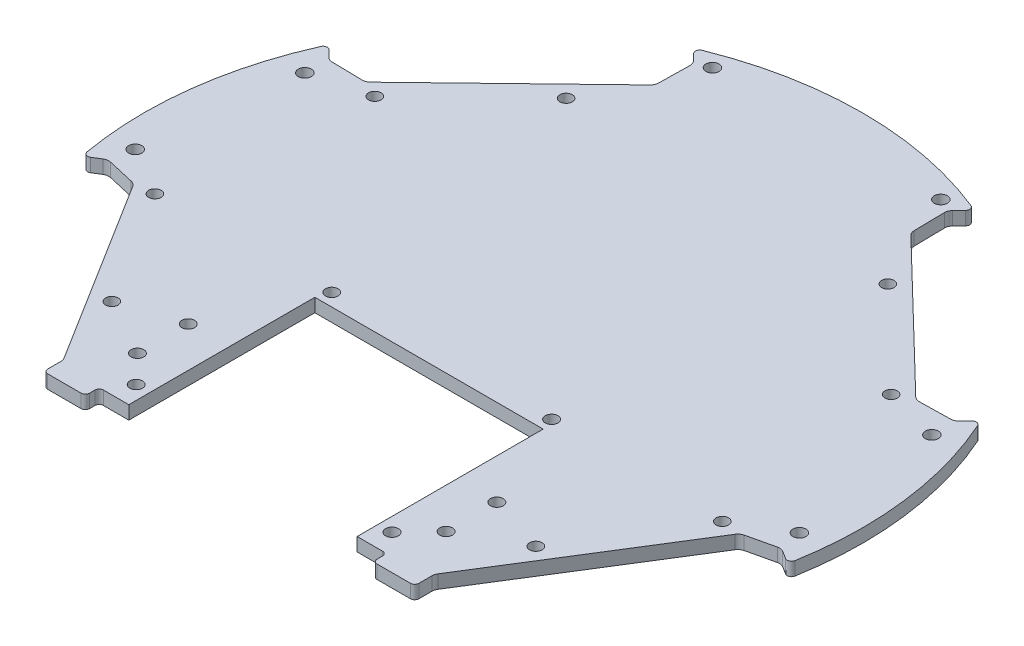
SolidWorks part; units mm, degrees
note: '?' marks a value the reader was unsure of.
material "6061 Alloy"
ref_plane "Front Plane" through (0, 0, 0) normal (0, 0, 1) x (1, 0, 0)
ref_plane "Top Plane" through (0, 0, 0) normal (0, 1, 0) x (1, 0, 0)
ref_plane "Right Plane" through (0, 0, 0) normal (1, 0, 0) x (0, 0, -1)
sketch "Sketch1" plane through (0, 0, 0) normal (0, 1, 0) x (1, 0, 0)
  line L0 (0, 0) -> (0, -62.55) construction
  line L1 (-83.4462, -16.178) -> (-71.2857, -8.5793) construction
  line L6 (0, 0) -> (-59.046, 61.1439) construction
  line L7 (0, 0) -> (-72.0841, -45.0431) construction
  line L8 (-33.174, 78.2591) -> (-23.2129, 67.9442) construction
  line L9 (-72.0841, -45.0431) -> (-70.388, -43.9833) construction
  line L10 (-70.388, -43.9833) -> (-84.9608, -20.662) construction
  line L11 (-84.9608, -20.662) -> (-72.2401, -12.7132) construction
  line L12 (-72.2401, -12.7132) -> (-43.0945, -59.3558) construction
  line L13 (-43.0945, -59.3558) -> (-55.8152, -67.3046) construction
  line L14 (-55.8152, -67.3046) -> (-70.388, -43.9833) construction
  line L21 (-59.046, 61.1439) -> (-57.6566, 59.7052)
  line L22 (-77.4385, 40.6021) -> (-37.8748, 78.8083) construction
  line L23 (-73.9694, 32.6911) -> (-77.0537, 35.885)
  line L24 (-37.8748, 78.8083) -> (-27.4549, 68.0182) construction
  line L25 (-27.4549, 68.0182) -> (-67.0186, 29.812) construction
  line L26 (-67.0186, 29.812) -> (-77.4385, 40.6021) construction
  line L27 (-43.0945, -64.8266) -> (-34, -64.8266)
  line L33 (-86.5505, -18.1178) -> (-71.2857, -8.5793) construction
  line L34 (0, 0) -> (0, 50000) construction
  line L35 (0, 0) -> (-50000, 0) construction
  line L36 (-57.5543, -62.55) -> (-19.8595, -62.55) construction
  line L38 (-67.0927, 25.57) -> (-79.5965, 38.5181) construction
  line L39 (-54.9774, -64.8266) -> (0, -64.8266) construction
  line L40 (-35.7168, 80.8923) -> (-23.2129, 67.9442) construction
  line L41 (-38.9606, -60.3102) -> (-54.2255, -69.8488) construction
  line L42 (-34, -62.55) -> (-19.8595, -62.55) construction
  line L43 (-43.0945, -64.8266) -> (-43.0945, -58.4123) construction
  line L45 (73.9694, 32.6911) -> (77.0537, 35.885)
  line L46 (-71.2857, -8.5793) -> (-38.9606, -60.3102) construction
  line L47 (83.4462, -16.178) -> (79.6809, -13.8252)
  line L48 (69.4846, -16.1792) -> (43.8945, -57.132)
  line L50 (43.0945, -64.8266) -> (34, -64.8266)
  line L51 (34, -62.55) -> (34, -64.8266)
  line L52 (0, 0) -> (72.0841, -45.0431) construction
  line L53 (0, 0) -> (59.046, 61.1439) construction
  line L54 (-30.0897, 75.0653) -> (-30.2847, 63.8954)
  line L55 (-62.7996, 32.4961) -> (-30.2847, 63.8954)
  line L56 (-30.0897, 75.0653) -> (-33.174, 78.2591)
  line L57 (73.9694, 32.6911) -> (77.0537, 35.885)
  line L58 (30.0897, 75.0653) -> (33.174, 78.2591)
  line L59 (-34, -62.55) -> (-34, -61.55)
  line L60 (62.7996, 32.4961) -> (30.2847, 63.8954)
  line L61 (-73.9694, 32.6911) -> (-62.7996, 32.4961)
  line L62 (-77.0537, 35.885) -> (-67.0927, 25.57) construction
  line L63 (-83.4462, -16.178) -> (-79.6809, -13.8252)
  line L64 (-79.6809, -13.8252) -> (-69.4846, -16.1792)
  line L65 (-69.4846, -16.1792) -> (-43.8945, -57.132)
  line L66 (-27.4549, 68.0182) -> (-23.2129, 67.9442) construction
  line L67 (-72.2401, -12.7132) -> (-71.2857, -8.5793) construction
  line L68 (30.0897, 75.0653) -> (30.2847, 63.8954)
  line L69 (73.9694, 32.6911) -> (62.7996, 32.4961)
  line L70 (-34, -62.55) -> (-34, -64.8266)
  line L71 (79.6809, -13.8252) -> (69.4846, -16.1792)
  line L72 (-34, -61.55) -> (-20, -61.55)
  line L73 (-20, -61.55) -> (-19.8595, -62.55)
  line L74 (-19.8595, -62.55) -> (19.8595, -62.55)
  line L75 (20, -61.55) -> (19.8595, -62.55)
  line L76 (34, -61.55) -> (20, -61.55)
  line L77 (34, -62.55) -> (34, -61.55)
  line L78 (-43.0945, -64.8266) -> (-43.8945, -64.8266)
  line L79 (-19.8595, -62.55) -> (0, -62.55) construction
  line L80 (-19.8595, -62.55) -> (34, -62.55) construction
  line L81 (-43.8945, -64.8266) -> (-43.8945, -57.132)
  line L82 (-43.0945, -58.4123) -> (-43.8945, -57.132) construction
  line L83 (43.8945, -64.8266) -> (43.8945, -57.132)
  line L84 (43.0945, -64.8266) -> (43.8945, -64.8266)
  line L97 (-23.2129, 67.9442) -> (-67.0927, 25.57) construction
  circle A0 centre (0, 0) radius 85 construction
  circle A1 centre (0, 0) radius 90 construction
  arc A51 (-77.0537, 35.885) -> (-83.4462, -16.178) centre (0, 0) ccw
  arc A52 (77.0537, 35.885) -> (83.4462, -16.178) centre (0, 0) cw
  arc A54 (-33.174, 78.2591) -> (33.174, 78.2591) centre (0, 0) cw
  point P29 (-31.6318, 76.6622)
  point P33 (-47.2368, 48.9151)
  point P34 (31.6318, 76.6622)
  point P35 (-57.6673, -36.0345)
  point P85 (-57.6566, 59.7052)
  dimension "D2" = 58
  dimension "D10" = 82
  dimension "D12" = 170
  dimension "D14" = 34
  dimension "D13" = 1
  dimension "D15" = 3
  dimension "D3" = 180
  dimension "D4" = 64.8266
  dimension "D5" = 44
  dimension "D6" = 15
  dimension "D7" = 55
  dimension "D8" = 62.55
  dimension "D9" = 2
  dimension "D11" = 2
  dimension "D16" = 7
  dimension "D17" = 7
  dimension "D18" = 0.5
  dimension "D19" = 1
  dimension "D20" = 14
  dimension "D21" = 0.8
extrude "Boss-Extrude4" add sketch "Sketch1" along normal mid plane 3.175
ref_point "Rear_Axle_Center (L)"
ref_axis "Rear_Axle_Proj (L)" through (46.5421, 0, -48.1958) along (0, 1, 0)?
ref_point "Front_Axle_Center (L)"
ref_axis "Front_Axle_Proj (L)" through (57.2432, 0, 35.7696) along (0, 1, 0)?
ref_point "Front_Axle_Center (R)"
ref_axis "Front_Axle_Proj (R)" through (-57.2432, 0, 35.7696) along (0, 1, 0)?
ref_point "Read_Axle_Center (R)"
ref_axis "Rear_Axle_Proj (R)" through (-46.5421, 0, -48.1958) along (0, 1, 0)?
sketch "Sketch17" plane through (0, 1.5875, 0) normal (0, 1, 0) x (1, 0, 0)
  line L0 (0, -57.55) -> (0, -62.55) construction
  line L1 (-19.8595, -62.55) -> (19.8595, -62.55) construction
  circle A0 centre (0, -57.55) radius 8.5
  dimension "D1" = 17
  dimension "D2" = 5
extrude "Boss-Extrude5" [suppressed] add sketch "Sketch17" against normal up to surface (3.175 mm away)
ref_plane "Plane1" through (0, 0, 10) normal (0, 0, 1) x (1, 0, 0)
hole_wizard "M3 Clearance Hole3" positions "Sketch18" profile "Sketch19" hole size "M3" standard "ANSI Metric" end condition through all
sketch "Sketch18" plane through (0, -1.5875, 0) normal (0, -1, 0) x (-1, 0, 0)
  line L0 (-36.5, -50) -> (-36.5, -38) construction
  line L3 (0, 0) -> (0, -38) construction
  line L4 (36.5, -50) -> (36.5, -38) construction
  line L6 (0, -38) -> (36.5, -38) construction
  line L8 (0, -38) -> (-36.5, -38) construction
  line L9 (-36.5, -44) -> (36.5, -44) construction
  line L10 (0, -44) -> (0, 0) construction
  point P1 (36.5, -50)
  point P3 (36.5, -38)
  point P5 (-36.5, -50)
  point P33 (-36.5, -38)
  dimension "D1" = 12
  dimension "D2" = 73
  dimension "D4" = 38
sketch "Sketch19" plane through (-36.5, -1.5875, 50) normal (1, 0, 0) x (0, 0, -1)
  line L0 (0, 0) -> (0, 3.175)
  line L1 (0, 3.175) -> (1.5, 3.175)
  line L2 (1.5, 3.175) -> (1.5, 0)
  line L5 (1.5, 0) -> (0, 0)
  line L11 (0, -6.35) -> (0, 107.95) construction
  dimension "Thru Hole Dia." = 3
  dimension "Thru Hole Depth" = 3.175
hole_wizard "M3 Clearance Hole1" positions "Sketch11" profile "Sketch12" hole size "M3" standard "ANSI Metric" end condition through all
sketch "Sketch11" plane through (0, 1.5875, 0) normal (0, 1, 0) x (1, 0, 0)
  line L0 (83.4462, -16.178) -> (79.6809, -13.8252) construction
  line L2 (73.9694, 32.6911) -> (77.0537, 35.885) construction
  line L4 (-73.9694, 32.6911) -> (-77.0537, 35.885) construction
  line L6 (0, 0) -> (0, -50000) construction
  line L7 (78.4111, 9.6277) -> (84.3664, 10.3589) construction
  line L10 (74.155, 27.2403) -> (78.5423, -8.4914) construction
  line L12 (78.4111, 9.6277) -> (76.3487, 9.3744) construction
  arc A7 (77.964, -12.7523) -> (72.563, 31.2347) centre (0, 0) ccw construction
  arc A13 (-77.964, -12.7523) -> (-72.563, 31.2347) centre (0, 0) cw construction
  arc A17 (83.4462, -16.178) -> (77.0537, 35.885) centre (0, 0) ccw construction
  point P34 (78.5423, -8.4914)
  point P66 (74.155, 27.2403)
  point P70 (-74.155, 27.2403)
  point P71 (-78.5423, -8.4914)
  dimension "D1" = 6
  dimension "D2" = 36
sketch "Sketch12" plane through (-78.5423, 1.5875, 8.4914) normal (1, 0, 0) x (0, 0, 1)
  line L0 (0, 0) -> (0, 3.175)
  line L1 (0, 3.175) -> (1.55, 3.175)
  line L2 (1.55, 3.175) -> (1.55, 0)
  line L5 (1.55, 0) -> (0, 0)
  line L11 (0, -6.35) -> (0, 107.95) construction
  dimension "Thru Hole Dia." = 3.1
  dimension "Thru Hole Depth" = 3.175
hole_wizard "M3 Clearance Hole4" positions "Sketch9" profile "Sketch10" hole size "M3" standard "ANSI Metric" end condition through all
sketch "Sketch9" plane through (0, -1.5875, 0) normal (0, -1, 0) x (-1, 0, 0)
  line L0 (0, 0) -> (0, 63.4318) construction
  line L1 (-38.0437, 52.9272) -> (38.0437, 52.9272) construction
  line L3 (61.0625, 30.6981) -> (-61.0625, 30.6981) construction
  line L4 (-67.0993, -15.2789) -> (67.0993, -15.2789) construction
  line L5 (50.1419, -42.4164) -> (-50.1419, -42.4164) construction
  line L6 (-61.0625, 30.6981) -> (-38.0437, 52.9272) construction
  line L7 (38.0437, 52.9272) -> (61.0625, 30.6981) construction
  line L8 (67.0993, -15.2789) -> (50.1419, -42.4164) construction
  line L9 (-50.1419, -42.4164) -> (-67.0993, -15.2789) construction
  line L10 (0, 0) -> (-44.8055, 46.3974) construction
  line L11 (0, 0) -> (44.8055, 46.3974) construction
  line L12 (0, 0) -> (-96.9468, 0) construction
  line L14 (-55.1231, -34.4448) -> (0, 0) construction
  line L15 (0, 0) -> (55.1231, -34.4448) construction
  line L18 (-69.4846, -16.1792) -> (-43.8945, -57.132) construction
  line L19 (-62.7996, 32.4961) -> (-30.2847, 63.8954) construction
  point P0 (-67.0993, -15.2789)
  point P2 (-50.1419, -42.4164)
  point P9 (-61.0625, 30.6981)
  point P11 (-38.0437, 52.9272)
  point P30 (50.1419, -42.4164)
  point P31 (67.0993, -15.2789)
  point P32 (38.0437, 52.9272)
  point P33 (61.0625, 30.6981)
  dimension "D9" = 46
  dimension "D10" = 46
  dimension "D11" = 32
  dimension "D12" = 32
  dimension "D7" = 58
  dimension "D5" = 32
  dimension "D6" = 2.5
  dimension "D8" = 9.4
  dimension "D2" = 44
  dimension "D3" = 32
  dimension "D4" = 2.5
  dimension "D13" = 9.4
sketch "Sketch10" plane through (67.0993, -1.5875, 15.2789) normal (1, 0, 0) x (0, 0, -1)
  line L0 (0, 0) -> (0, 3.175)
  line L1 (0, 3.175) -> (1.475, 3.175)
  line L2 (1.475, 3.175) -> (1.475, 0)
  line L5 (1.475, 0) -> (0, 0)
  line L11 (0, -6.35) -> (0, 107.95) construction
  dimension "Thru Hole Dia." = 2.95
  dimension "Thru Hole Depth" = 3.175
hole_wizard "M3 Clearance Hole2" positions "Sketch13" profile "Sketch14" hole size "M3" standard "ANSI Metric" end condition through all
sketch "Sketch13" plane through (0, 1.5875, 0) normal (0, 1, 0) x (1, 0, 0)
  line L0 (0, 0) -> (0, 85) construction
  line L2 (-24, 47) -> (-24, 81) construction
  line L3 (-24, 47) -> (24, 47) construction
  line L4 (-24, 81) -> (24, 81) construction
  line L5 (24, 47) -> (24, 81) construction
  line L6 (-24, 47) -> (24, 81) construction
  line L7 (-24, 81) -> (24, 47) construction
  line L8 (-38.0437, 52.9272) -> (-61.0625, 30.6981) construction
  line L10 (-36.307, 51.1289) -> (-59.3259, 28.8998) construction
  line L11 (-16.3488, 39.8187) -> (-31.6313, 55.6441) construction
  line L12 (-16.3488, 39.8187) -> (-48.7191, 8.559) construction
  line L13 (-31.6313, 55.6441) -> (-64.0016, 24.3845) construction
  line L14 (-48.7191, 8.559) -> (-64.0016, 24.3845) construction
  line L15 (-16.3488, 39.8187) -> (-64.0016, 24.3845) construction
  line L16 (-31.6313, 55.6441) -> (-48.7191, 8.559) construction
  line L17 (-49.5531, 41.8127) -> (-40.1752, 32.1016) construction
  line L18 (-27, 76.4978) -> (-27, 80.5978) construction
  arc A0 (33.174, 78.2591) -> (-33.174, 78.2591) centre (0, 0) ccw construction
  circle A1 centre (-16.2162, 44) radius 3 construction
  circle A2 centre (-27, 76.4978) radius 3 construction
  point P65 (0, 64)
  point P181 (-27, 76.4978)
  point P184 (27, 76.4978)
  dimension "D7" = 6
  dimension "D1" = 48
  dimension "D2" = 34
  dimension "D3" = 4
  dimension "D5" = 45
  dimension "D6" = 22
  dimension "D8" = 4.1
  dimension "D4" = 2.5
sketch "Sketch14" plane through (27, 1.5875, -76.4978) normal (1, 0, 0) x (0, 0, 1)
  line L0 (0, 0) -> (0, 3.175)
  line L1 (0, 3.175) -> (1.55, 3.175)
  line L2 (1.55, 3.175) -> (1.55, 0)
  line L5 (1.55, 0) -> (0, 0)
  line L11 (0, -6.35) -> (0, 107.95) construction
  dimension "Thru Hole Dia." = 3.1
  dimension "Thru Hole Depth" = 3.175
hole_wizard "M3 Clearance Hole5" [suppressed] positions "Sketch24" profile "Sketch25" hole size "M3" standard "ANSI Metric"
sketch "Sketch24" plane through (0, 1.5875, 0) normal (0, 1, 0) x (1, 0, 0)
  line L1 (-11, -4.4) -> (11, -4.4) construction
  line L2 (11, -4.4) -> (11, -36.4) construction
  line L3 (11, -36.4) -> (-11, -36.4) construction
  line L4 (-11, -36.4) -> (-11, -4.4) construction
  line L7 (-11, 37.6) -> (11, 37.6) construction
  line L8 (0, -4.4) -> (0, 0) construction
  line L9 (0, 0) -> (0, 37.6) construction
  point P8 (-11, -4.4)
  point P10 (11, -4.4)
  point P12 (11, -36.4)
  point P14 (-11, -36.4)
  point P42 (-11, 37.6)
  point P45 (11, 37.6)
  dimension "D1" = 22
  dimension "D2" = 32
  dimension "D3" = 4.4
  dimension "D4" = 42
sketch "Sketch25" plane through (-11, 1.5875, 4.4) normal (1, 0, 0) x (0, 0, 1)
  line L0 (0, 0) -> (0, 3.175)
  line L1 (0, 3.175) -> (1.5, 3.175)
  line L2 (1.5, 3.175) -> (1.5, 0)
  line L5 (1.5, 0) -> (0, 0)
  line L11 (0, -6.35) -> (0, 107.95) construction
  dimension "Thru Hole Dia." = 3
  dimension "Thru Hole Depth" = 3.175
sketch "Sketch20" plane through (0, 1.5875, 0) normal (0, 1, 0) x (1, 0, 0)
  line L0 (-16.1485, 44) -> (-16.1485, 39) construction
  line L1 (-14.6485, 44) -> (-14.6485, 39)
  line L2 (-17.6485, 44) -> (-17.6485, 39)
  line L3 (0, 0) -> (0, 85) construction
  line L5 (16.1485, 44) -> (16.1485, 39) construction
  line L6 (14.6485, 44) -> (14.6485, 39)
  line L7 (17.6485, 44) -> (17.6485, 39)
  arc A0 (-14.6485, 44) -> (-17.6485, 44) centre (-16.1485, 44) ccw
  arc A1 (-17.6485, 39) -> (-14.6485, 39) centre (-16.1485, 39) ccw
  arc A5 (33.174, 78.2591) -> (-33.174, 78.2591) centre (0, 0) ccw construction
  arc A7 (14.6485, 44) -> (17.6485, 44) centre (16.1485, 44) cw
  arc A8 (17.6485, 39) -> (14.6485, 39) centre (16.1485, 39) cw
  point P2 (-16.1485, 41.5)
  point P16 (16.1485, 41.5)
  dimension "D1" = 44
  dimension "D2" = 3
  dimension "D3" = 5
  dimension "D4" = 16.1485
extrude "Cut-Extrude1" [suppressed] cut sketch "Sketch20" against normal through all
sketch "Sketch22" plane through (0, 1.5875, 0) normal (0, 1, 0) x (1, 0, 0)
  line L0 (-56.6896, -36.6556) -> (-58.0464, -37.5035) construction
  line L1 (-69.4846, -16.1792) -> (-43.8945, -57.132) construction
  line L3 (30.2452, 66.1578) -> (65.062, 32.5356)
  line L4 (71.6894, -15.6702) -> (43.8945, -60.1514)
  line L5 (-19.8595, -62.55) -> (19.8595, -62.55) construction
  line L6 (-43.8945, -64.8266) -> (-43.8945, -57.132) construction
  line L28 (-30.2452, 66.1578) -> (-65.062, 32.5356)
  line L29 (-71.6894, -15.6702) -> (-43.8945, -60.1514)
  line L30 (-79.6809, -13.8252) -> (-69.4846, -16.1792) construction
  line L31 (0, 85) -> (0, -62.55) construction
  line L32 (-46.5421, 48.1958) -> (-47.6536, 49.3467) construction
  line L37 (-20, -61.55) -> (-19.8595, -62.55)
  line L38 (-20, -61.55) -> (-19.8595, -62.55)
  line L40 (-43.8945, -57.132) -> (-43.8945, -64.8266)
  line L41 (-43.8945, -57.132) -> (-43.8945, -64.8266)
  line L43 (43.8945, -64.8266) -> (43.8945, -57.132)
  line L44 (43.8945, -64.8266) -> (43.8945, -57.132)
  line L56 (-19.8595, -62.55) -> (19.8595, -62.55)
  line L58 (19.8595, -62.55) -> (20, -61.55)
  line L59 (20, -61.55) -> (34, -61.55)
  line L60 (34, -61.55) -> (34, -64.8266)
  line L61 (34, -64.8266) -> (43.8945, -64.8266)
  line L63 (43.8945, -57.132) -> (69.4846, -16.1792)
  line L64 (69.4846, -16.1792) -> (79.6809, -13.8252)
  line L65 (79.6809, -13.8252) -> (83.4462, -16.178)
  line L66 (77.0537, 35.885) -> (73.9694, 32.6911)
  line L67 (73.9694, 32.6911) -> (62.7996, 32.4961)
  line L68 (62.7996, 32.4961) -> (30.2847, 63.8954)
  line L69 (30.2847, 63.8954) -> (30.0897, 75.0653)
  line L70 (30.0897, 75.0653) -> (33.174, 78.2591)
  line L71 (-33.174, 78.2591) -> (-30.0897, 75.0653)
  line L72 (-30.0897, 75.0653) -> (-30.2847, 63.8954)
  line L73 (-30.2847, 63.8954) -> (-62.7996, 32.4961)
  line L74 (-62.7996, 32.4961) -> (-73.9694, 32.6911)
  line L75 (-73.9694, 32.6911) -> (-77.0537, 35.885)
  line L76 (-83.4462, -16.178) -> (-79.6809, -13.8252)
  line L77 (-79.6809, -13.8252) -> (-69.4846, -16.1792)
  line L78 (-69.4846, -16.1792) -> (-43.8945, -57.132)
  line L80 (-43.8945, -64.8266) -> (-34, -64.8266)
  line L81 (-34, -64.8266) -> (-34, -61.55)
  line L82 (-34, -61.55) -> (-20, -61.55)
  line L84 (-19.8595, -62.55) -> (19.8595, -62.55)
  line L86 (19.8595, -62.55) -> (20, -61.55)
  line L87 (20, -61.55) -> (34, -61.55)
  line L88 (34, -61.55) -> (34, -64.8266)
  line L89 (34, -64.8266) -> (43.8945, -64.8266)
  line L91 (43.8945, -57.132) -> (69.4846, -16.1792)
  line L92 (69.4846, -16.1792) -> (79.6809, -13.8252)
  line L93 (79.6809, -13.8252) -> (83.4462, -16.178)
  line L94 (77.0537, 35.885) -> (73.9694, 32.6911)
  line L95 (73.9694, 32.6911) -> (62.7996, 32.4961)
  line L96 (62.7996, 32.4961) -> (30.2847, 63.8954)
  line L97 (30.2847, 63.8954) -> (30.0897, 75.0653)
  line L98 (30.0897, 75.0653) -> (33.174, 78.2591)
  line L99 (-33.174, 78.2591) -> (-30.0897, 75.0653)
  line L100 (-30.0897, 75.0653) -> (-30.2847, 63.8954)
  line L101 (-30.2847, 63.8954) -> (-62.7996, 32.4961)
  line L102 (-62.7996, 32.4961) -> (-73.9694, 32.6911)
  line L103 (-73.9694, 32.6911) -> (-77.0537, 35.885)
  line L104 (-83.4462, -16.178) -> (-79.6809, -13.8252)
  line L105 (-79.6809, -13.8252) -> (-69.4846, -16.1792)
  line L106 (-69.4846, -16.1792) -> (-43.8945, -57.132)
  line L108 (-43.8945, -64.8266) -> (-34, -64.8266)
  line L109 (-34, -64.8266) -> (-34, -61.55)
  line L110 (-34, -61.55) -> (-20, -61.55)
  arc A9 (83.4462, -16.178) -> (77.0537, 35.885) centre (0, 0) ccw
  arc A10 (33.174, 78.2591) -> (-33.174, 78.2591) centre (0, 0) ccw
  arc A11 (-77.0537, 35.885) -> (-83.4462, -16.178) centre (0, 0) ccw
  arc A13 (83.4462, -16.178) -> (77.0537, 35.885) centre (0, 0) ccw
  arc A14 (33.174, 78.2591) -> (-33.174, 78.2591) centre (0, 0) ccw
  arc A15 (-77.0537, 35.885) -> (-83.4462, -16.178) centre (0, 0) ccw
  dimension "D2" = 1.6
  dimension "D1" = 0
extrude "Boss-Extrude6" add sketch "Sketch22" against normal up to surface (3.175 mm away) up to face at (-27, -1.5875, -74.9478)
fillet "Fillet1" radius 2 14 edges at (-30.0897, 0, -75.0653) (30.0897, 0, -75.0653) (-79.6809, 0, 13.8252) (79.6809, 0, 13.8252) (73.9694, 0, -32.6911) (-73.9694, 0, -32.6911) (65.062, 0, -32.5356) (30.2452, 0, -66.1578) (71.6894, 0, 15.6702) (-71.6894, 0, 15.6702) (-65.062, 0, -32.5356) (-30.2452, 0, -66.1578) (43.8945, 0, 60.1514) (-43.8945, 0, 60.1514)
fillet "Fillet3" radius 1 12 edges at (-77.0537, 0, -35.885) (77.0537, 0, -35.885) (83.4462, 0, 16.178) (34, 0, 64.8266) (-34, 0, 64.8266) (-33.174, 0, -78.2591) (33.174, 0, -78.2591) (-83.4462, 0, 16.178) (34, 0, 61.55) (-34, 0, 61.55) (-43.8945, 0, 64.8266) (43.8945, 0, 64.8266)
sketch "Sketch23" [suppressed] plane through (0, 3.175, 0) normal (0, 1, 0) x (1, 0, 0)
  circle A0 centre (0, -53.55) radius 4.95
  dimension "D1" = 9.9
fillet "Fillet6" radius 0.5 4 edges at (20, 0, 61.55) (19.8595, 0, 62.55) (-20, 0, 61.55) (-19.8595, 0, 62.55)
sketch "Sketch28" plane through (0, 1.5875, 0) normal (0, 1, 0) x (1, 0, 0)
  line L0 (-19.4248, -62.55) -> (19.4248, -62.55) construction
  line L1 (-19.4248, -62.55) -> (19.4248, -62.55) construction
  line L2 (-27, -62.55) -> (27, -62.55)
  line L3 (-27, -62.55) -> (-27, -17.55)
  line L4 (27, -62.55) -> (27, -17.55)
  line L5 (-27, -17.55) -> (27, -17.55)
  line L6 (0, 15.921) -> (0, -77.8833) construction
  arc A0 (19.4248, -62.55) -> (19.9199, -62.1196) centre (19.4248, -62.05) ccw construction
  point P11 (0, -62.55)
  point P16 (0, -17.55)
  dimension "D1" = 54
  dimension "D2" = 45
extrude "Cut-Extrude4" cut sketch "Sketch28" against normal blind 10
extrude "Cut-Extrude2" [suppressed] cut sketch "Sketch23" against normal through all
sketch "Sketch26" [suppressed] plane through (0, 3.175, 0) normal (0, 1, 0) x (1, 0, 0)
  line L0 (0, 0) -> (0, 50) construction
  line L1 (-92.5, 5) -> (92.5, 5)
  line L2 (-92.5, 5) -> (-92.5, 95)
  line L3 (-92.5, 95) -> (92.5, 95)
  line L4 (92.5, 5) -> (92.5, 95)
  line L5 (-92.5, 5) -> (92.5, 95) construction
  line L6 (-92.5, 95) -> (92.5, 5) construction
  point P0 (0, 50)
  dimension "D1" = 90
  dimension "D2" = 185
  dimension "D3" = 5
extrude "Cut-Extrude3" [suppressed] cut sketch "Sketch26" against normal through all
fillet "Fillet4" [suppressed] radius 5
sketch "Sketch29" plane through (0, 1.5875, 0) normal (0, 1, 0) x (1, 0, 0)
  line L0 (-27, -61.55) -> (-27, -56.55)
  line L2 (-27, -17.55) -> (-27, -61.55) construction
  line L3 (-27, -56.55) -> (-33.3126, -56.55) construction
  line L4 (-27, -56.55) -> (-30.25, -56.55)
  line L5 (27, -56.55) -> (30.25, -56.55)
  line L6 (27, -61.55) -> (27, -17.55) construction
  circle A0 centre (30.25, -56.55) radius 1.5
  circle A1 centre (-30.25, -56.55) radius 1.5
  dimension "D4" = 3
  dimension "D5" = 3
  dimension "D1" = 5
  dimension "D2" = 3.25
  dimension "D3" = 3.25
extrude "Cut-Extrude5" cut sketch "Sketch29" against normal blind 10 contours L4 L3 A1 | L3 L4 A1 | A0 L3 L5 | L3 A0 L5
sketch "Sketch31" plane through (0, 1.5875, 0) normal (0, 1, 0) x (1, 0, 0)
  line L0 (27, -17.55) -> (-27, -17.55) construction
  line L1 (0, 35.8655) -> (0, -81.8862) construction
  circle A0 centre (-26, -14.55) radius 1.5
  circle A1 centre (26, -14.55) radius 1.5
  dimension "D3" = 3
  dimension "D1" = 52
  dimension "D2" = 3
extrude "Cut-Extrude7" cut sketch "Sketch31" against normal blind 10
sketch "Sketch32" plane through (0, 1.5875, 0) normal (0, 1, 0) x (1, 0, 0)
  line L0 (-43.6016, -64.5337) -> (43.6016, -64.5337)
  line L1 (-43.6016, -64.5337) -> (-43.6016, 20.2064)
  line L2 (43.6016, -64.5337) -> (43.6016, 20.2064)
  line L3 (-43.6016, 20.2064) -> (43.6016, 20.2064)
  arc A0 (-43.8945, -63.8266) -> (-42.8945, -64.8266) centre (-42.8945, -63.8266) ccw construction
  arc A1 (42.8945, -64.8266) -> (43.8945, -63.8266) centre (42.8945, -63.8266) ccw construction
extrude "Cut-Extrude8" [suppressed] cut sketch "Sketch32" against normal blind 10 flip side to cut
sketch "Sketch33" [suppressed] plane through (0, -1.5875, 0) normal (0, -1, 0) x (1, 0, 0)
  line L0 (-43.6016, 64.5337) -> (-34.2929, 64.5337)
  line L1 (-43.6016, 64.5337) -> (-43.6016, 54.5337)
  line L2 (-34.2929, 64.5337) -> (-34.2929, 54.5337)
  line L3 (-43.6016, 54.5337) -> (-34.2929, 54.5337)
  line L4 (43.6016, 64.5337) -> (34.2929, 64.5337)
  line L5 (43.6016, 64.5337) -> (43.6016, 54.5337)
  line L6 (34.2929, 64.5337) -> (34.2929, 54.5337)
  line L7 (43.6016, 54.5337) -> (34.2929, 54.5337)
  line L9 (-43.6016, -20.2064) -> (-33.6016, -20.2064)
  line L10 (-43.6016, -20.2064) -> (-43.6016, -10.2064)
  line L11 (-43.6016, -10.2064) -> (-33.6016, -10.2064)
  line L12 (-33.6016, -20.2064) -> (-33.6016, -10.2064)
  line L13 (43.6016, -20.2064) -> (33.6016, -20.2064)
  line L14 (43.6016, -20.2064) -> (43.6016, -10.2064)
  line L15 (43.6016, -10.2064) -> (33.6016, -10.2064)
  line L16 (33.6016, -20.2064) -> (33.6016, -10.2064)
  dimension "D1" = 10
  dimension "D2" = 10
  dimension "D3" = 10
  dimension "D4" = 10
  dimension "D5" = 10
  dimension "D6" = 10
extrude "Boss-Extrude7" [suppressed] add sketch "Sketch33" along normal blind 5
equation "\"D3@Sketch9\"=\"D5@Sketch9\""
equation "\"D4@Sketch9\"=\"D6@Sketch9\""
equation "\"D13@Sketch9\"=\"D8@Sketch9\""
